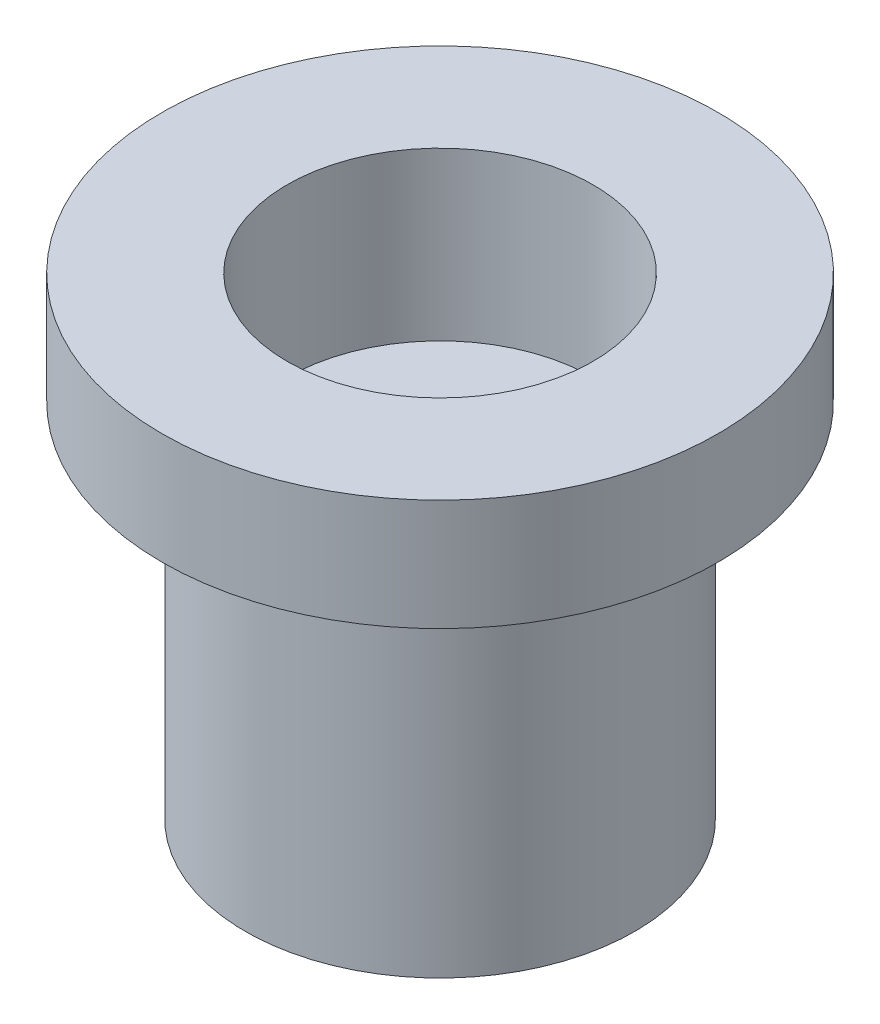
SolidWorks part; units mm, degrees
material "PLA - 20% infill"
ref_plane "Front Plane" through (0, 0, 0) normal (0, 0, 1) x (1, 0, 0)
ref_plane "Top Plane" through (0, 0, 0) normal (0, 1, 0) x (1, 0, 0)
ref_plane "Right Plane" through (0, 0, 0) normal (1, 0, 0) x (0, 0, -1)
sketch "Sketch2" plane through (0, 0, 0) normal (0, 1, 0) x (1, 0, 0)
  circle A0 centre (0, 0) radius 3.5
  dimension "D1" = 7
extrude "Boss-Extrude1" add sketch "Sketch2" along normal blind 6.5
sketch "Sketch3" plane through (0, 6.5, 0) normal (0, 1, 0) x (1, 0, 0)
  circle A0 centre (0, 0) radius 5
  dimension "D1" = 10
extrude "Boss-Extrude2" add sketch "Sketch3" along normal blind 2
sketch "Sketch4" plane through (0, 0, 0) normal (0, -1, 0) x (1, 0, 0)
  circle A0 centre (0, 0) radius 1.25
  dimension "D1" = 2.5
extrude "Cut-Extrude1" cut sketch "Sketch4" against normal offset from surface (6.5 mm away) 2 up to face at (0, 8.5, 5)
sketch "Sketch5" plane through (0, 8.5, 0) normal (0, 1, 0) x (1, 0, 0)
  circle A0 centre (0, 0) radius 2.75
  dimension "D1" = 5.5
extrude "Cut-Extrude2" cut sketch "Sketch5" against normal blind 3
